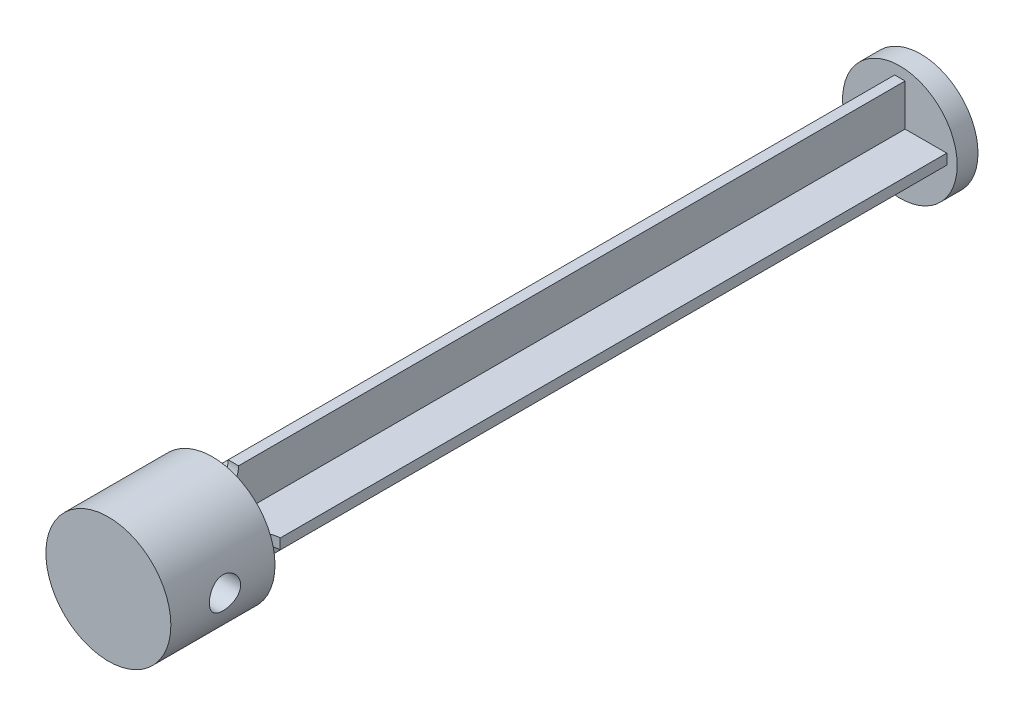
SolidWorks part; units mm, degrees
material "ABS"
ref_plane "Front" through (0, 0, 0) normal (0, 0, 1) x (1, 0, 0)
ref_plane "Top" through (0, 0, 0) normal (0, 1, 0) x (1, 0, 0)
ref_plane "Right" through (0, 0, 0) normal (1, 0, 0) x (0, 0, -1)
sketch "Sketch1" plane through (0, 0, 0) normal (0, 0, 1) x (1, 0, 0)
  circle A0 centre (0, 0) radius 6.985
  dimension "D1" = 13.97
extrude "Boss-Extrude1" add sketch "Sketch1" along normal blind 2.54
sketch "Sketch2" plane through (0, 0, 2.54) normal (0, 0, 1) x (1, 0, 0)
  line L0 (-0.635, 0.635) -> (-0.635, -0.635) construction
  line L1 (-0.635, -0.635) -> (-5.715, -0.635)
  line L3 (-0.635, 0.635) -> (-5.715, 0.635)
  line L4 (-5.715, -0.635) -> (-5.715, 0.635)
  line L6 (-0.635, 0.635) -> (-0.635, 5.715)
  line L7 (-0.635, 5.715) -> (0.635, 5.715)
  line L8 (0.635, 0.635) -> (0.635, 5.715)
  line L9 (0.635, -0.635) -> (5.715, -0.635)
  line L11 (0.635, 0.635) -> (5.715, 0.635)
  line L12 (5.715, -0.635) -> (5.715, 0.635)
  line L14 (0.635, -0.635) -> (0.635, -5.715)
  line L15 (0.635, -5.715) -> (-0.635, -5.715)
  line L16 (-0.635, -0.635) -> (-0.635, -5.715)
  line L17 (-0.635, 0.635) -> (0.635, 0.635) construction
  point P2 (-0.635, 0)
  point P13 (0, 0.635)
  point P14 (0, 0)
  dimension "D1" = 5.08
  dimension "D2" = 1.27
extrude "Boss-Extrude2" add sketch "Sketch2" along normal blind 81.28
sketch "Sketch3" plane through (0, 0, 83.82) normal (0, 0, 1) x (1, 0, 0)
  line L1 (-3.175, 0.635) -> (-0.635, 0.635)
  line L2 (-3.175, 0.635) -> (-3.175, -0.635)
  line L3 (-3.175, -0.635) -> (-0.635, -0.635)
  line L5 (-0.635, 3.175) -> (0.635, 3.175)
  line L6 (-0.635, 3.175) -> (-0.635, 0.635)
  line L8 (0.635, 3.175) -> (0.635, 0.635)
  line L9 (3.175, 0.635) -> (0.635, 0.635)
  line L10 (3.175, 0.635) -> (3.175, -0.635)
  line L11 (3.175, -0.635) -> (0.635, -0.635)
  line L14 (0.635, -0.635) -> (5.715, -0.635) construction
  line L15 (0.635, -3.175) -> (-0.635, -3.175)
  line L16 (0.635, -3.175) -> (0.635, -0.635)
  line L18 (-0.635, -3.175) -> (-0.635, -0.635)
  line L19 (0.635, 5.715) -> (-0.635, 5.715) construction
  line L20 (5.715, -0.635) -> (5.715, 0.635) construction
  line L21 (-5.715, 0.635) -> (-5.715, -0.635) construction
  line L22 (-0.635, -5.715) -> (0.635, -5.715) construction
  line L23 (-0.635, 0.635) -> (-5.715, 0.635) construction
  line L24 (-0.635, 5.715) -> (-0.635, 0.635) construction
  dimension "D1" = 2.54
  dimension "D2" = 2.54
  dimension "D3" = 2.54
  dimension "D4" = 2.54
extrude "Boss-Extrude3" add sketch "Sketch3" along normal blind 2.54
fillet "Fillet1" radius 2.54 4 edges at (0, -3.175, 83.82) (3.175, 0, 83.82) (0, 3.175, 83.82) (-3.175, 0, 83.82)
sketch "Sketch4" plane through (0, 0, 86.36) normal (0, 0, 1) x (1, 0, 0)
  circle A0 centre (0, 0) radius 7.62
  dimension "D1" = 15.24
extrude "Boss-Extrude4" add sketch "Sketch4" along normal blind 12.7
sketch "Sketch5" plane through (5.715, 0, 0) normal (1, 0, 0) x (0, 0, -1)
  line L0 (-83.82, -0.635) -> (-83.82, 0.635) construction
  circle A0 centre (-92.4585, 0) radius 1.905
  point P3 (-83.82, 0)
  dimension "D1" = 3.81
extrude "Cut-Extrude1" cut sketch "Sketch5" against normal through all both and the other way through all
equation "\"D2@Sketch3\"=\"D1@Sketch3\""
equation "\"D3@Sketch3\"=\"D1@Sketch3\""
equation "\"D4@Sketch3\"=\"D1@Sketch3\""
